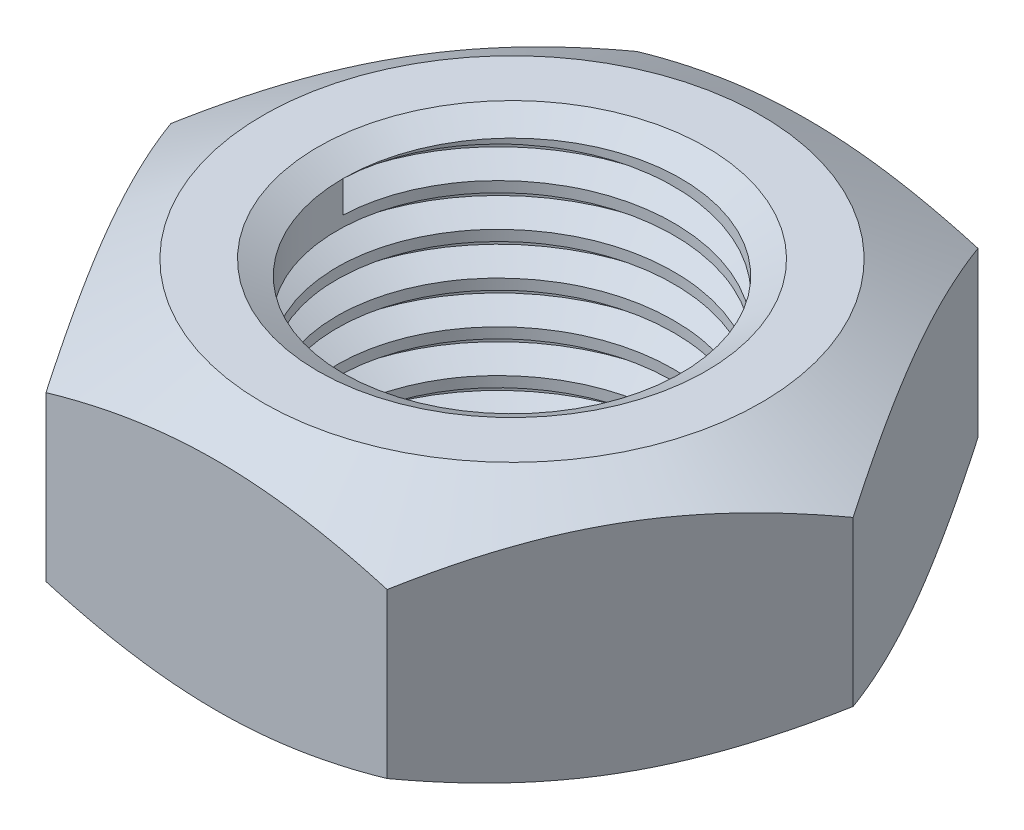
SolidWorks part; units mm, degrees
ref_plane "Alzado" through (0, 0, 0) normal (0, 0, 1) x (1, 0, 0)
ref_plane "Planta" through (0, 0, 0) normal (0, 1, 0) x (1, 0, 0)
ref_plane "Vista lateral" through (0, 0, 0) normal (1, 0, 0) x (0, 0, -1)
sketch "Croquis1" plane through (0, 0, 0) normal (0, 1, 0) x (1, 0, 0)
  line L1 (4.0415, 0) -> (2.0207, 3.5)
  line L2 (2.0207, 3.5) -> (-2.0207, 3.5)
  line L3 (-2.0207, 3.5) -> (-4.0415, 0)
  line L4 (-4.0415, 0) -> (-2.0207, -3.5)
  line L5 (-2.0207, -3.5) -> (2.0207, -3.5)
  line L6 (2.0207, -3.5) -> (4.0415, 0)
  circle A0 centre (0, 0) radius 3.5 construction
  dimension "S" = 7
extrude "Saliente-Extruir1" add sketch "Croquis1" along normal blind 3.2
ref_axis "Eje1" through (0, 2.52, 0) along (0, -1, 0)
sketch "Croquis3" plane through (0, 0, 0) normal (0, 0, 1) x (1, 0, 0)
  line L0 (2.95, 3.2) -> (4.0415, 2.5698)
  line L1 (2.0207, 3.2) -> (4.0415, 3.2) construction
  line L2 (4.0415, 3.2) -> (4.0415, 0) construction
  line L3 (0, -3.048) -> (0, 3.048) construction
  spline S0 degree 3 poles (2.95, 3.2) (2.5959, 12.0139) (18.88, 3.5442) (4.0415, 2.5698) knots 0 0 0 0 1 1 1 1
  dimension "D1" = 30
  dimension "dw" = 2.95
revolve "Cortar-Revolución1" cut sketch "Croquis3" angle 360 about axis through (0, 2.52, 0) along (0, -1, 0)
sketch "Croquis4" plane through (0, 3.2, 0) normal (0, 1, 0) x (1, 0, 0)
  circle A0 centre (0, 0) radius 2
  dimension "D1" = 4
extrude "Cortar-Extruir1" cut sketch "Croquis4" against normal through all
sketch "Croquis5" plane through (0, 0, 0) normal (0, 0, 1) x (1, 0, 0)
  line L0 (0.9445, 2.4174) -> (2.3, 3.2)
  line L2 (2.95, 3.2) -> (-2.95, 3.2) construction
  line L3 (0, -3.048) -> (0, 3.048) construction
  spline S0 degree 3 poles (2.3, 3.2) (6.2705, 12.3882) (-1.281, 4.3186) (0.9445, 2.4174) knots 0 0 0 0 1 1 1 1
  dimension "D1" = 60
  dimension "da" = 2.3
revolve "Cortar-Revolución2" cut sketch "Croquis5" angle 360 about axis through (0, 2.52, 0) along (0, -1, 0)
ref_plane "Plano1" through (0, 1.6, 0) normal (0, -1, 0) x (-1, 0, 0)
mirror "Simetría1" about plane through (0, 1.6, 0) normal (0, -1, 0) of "Cortar-Revolución2", "Cortar-Revolución1"
thread "RoscaM3" pitch 0.5 method cut trim with start face yes trim with end face yes profile "Perfil de rosca1" start angle 0, offset 0, length 0, pitch 0.5, diameter 4
ref_plane "Plano2" through (-2, 3.0268, 0) normal (0, 0, 1) x (-1, 0, 0)
sketch "Perfil de rosca1" plane through (-2, 3.0268, 0) normal (0, 0, 1) x (-1, 0, 0)
  line L0 (0, 0) -> (0, 0.5) construction
  line L1 (0, 0) -> (0.2706, 0.1562)
  line L2 (0.2706, 0.1562) -> (0.2706, 0.2187)
  line L3 (0.2706, 0.2187) -> (0, 0.375)
  line L4 (0.2706, 0.1875) -> (0, 0.1875) construction
  line L11 (0, 0) -> (0, 0.375)
  point P2 (0, 0)
  dimension "Pitch" = 0.5
  dimension "Profile_Angle" = 60
  dimension "Profile_Land" = 0.0625
  dimension "Profile_Height" = 0.2706
thread "RoscaM6" [suppressed] pitch 1 start angle 0, offset 0, length 0, pitch 1, diameter 6
ref_plane "Plano3" through (-3, 4.9835, 0) normal (0, 0, 1) x (-1, 0, 0)
sketch "Perfil de rosca2" plane through (-3, 4.9835, 0) normal (0, 0, 1) x (-1, 0, 0)
  line L0 (0, 0) -> (0, 1) construction
  line L1 (0, 0) -> (0.5413, 0.3125)
  line L2 (0.5413, 0.3125) -> (0.5413, 0.4375)
  line L3 (0.5413, 0.4375) -> (0, 0.75)
  line L4 (0.5413, 0.375) -> (0, 0.375) construction
  line L11 (0, 0) -> (0, 0.75)
  point P2 (0, 0)
  dimension "Pitch" = 1
  dimension "Profile_Angle" = 60
  dimension "Profile_Land" = 0.125
  dimension "Profile_Height" = 0.5413
